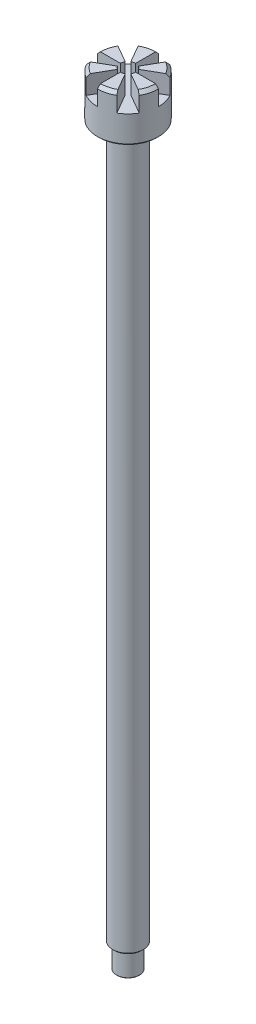
SolidWorks part; units mm, degrees
note: '?' marks a value the reader was unsure of.
ref_plane "Front Plane" through (0, 0, 0) normal (0, 0, 1) x (1, 0, 0)
ref_plane "Top Plane" through (0, 0, 0) normal (0, 1, 0) x (1, 0, 0)
ref_plane "Right Plane" through (0, 0, 0) normal (1, 0, 0) x (0, 0, -1)
sketch "Sketch1" plane through (0, 0, 0) normal (0, 0, 1) x (1, 0, 0)
  line L2 (0, 0) -> (0, 40)
  line L3 (0, 40) -> (20, 40)
  line L4 (20, 40) -> (20, 10)
  line L5 (20, 10) -> (10, 10)
  line L6 (10, 10) -> (10, 0)
  line L7 (10, 0) -> (0, 0)
  dimension "D1" = 10
  dimension "D2" = 10
  dimension "D4" = 40
  dimension "D6" = 20
revolve "Revolve1" add sketch "Sketch1" angle 360 about L2
ref_axis "Axis1" through (0, 40, 0) along (0, -1, 0)?
chamfer "Chamfer1" distance 2 angle 45 1 edges at (0, 40, -20)
sketch "Sketch2" plane through (0, 40, 0) normal (0, 1, 0) x (1, 0, 0)
  line L0 (0, 0) -> (0, 21.1426)
  line L1 (0, 21.1426) -> (12.2067, 21.1426)
  line L2 (12.2067, 21.1426) -> (0, 0)
  circle A0 centre (0, 0) radius 5
  circle M4 centre (0, 0) radius 18
  dimension "D2" = 10
  dimension "D1" = 30
extrude "Cut-Extrude1" cut sketch "Sketch2" against normal blind 12 contours A0 L2 L0 M4 | L2 L1 L0 M4
pattern_circular "CirPattern6" count 6 over 360 about axis through (0, 0, 0) along (0, 1, 0) of "Cut-Extrude1"
sketch "Sketch3" plane through (0, 40, 0) normal (0, 1, 0) x (1, 0, 0)
  circle A0 centre (0, 0) radius 5
  arc A1 (2.5, 4.3301) -> (0, 5) centre (0, 0) ccw construction
extrude "Cut-Extrude2" cut sketch "Sketch3" against normal up to surface (12 mm away)
chamfer "Chamfer2" distance 1 angle 45 2 edges at (0, 10, -20) (0, 10, -10)
sketch "Sketch4" plane through (0, 0, 0) normal (0, 0, 1) x (1, 0, 0)
  line L0 (0, 0) -> (0, -510)
  line L1 (0, -510) -> (10, -510)
  line L2 (10, -510) -> (10, 0)
  line L3 (10, 0) -> (0, 0)
  line L4 (10, 0) -> (10, 9) construction
  dimension "D1" = 510
revolve "Revolve2" add sketch "Sketch4" angle 360 about L0
sketch "Sketch5" plane through (0, -510, 0) normal (0, -1, 0) x (1, 0, 0)
  circle A0 centre (0, 0) radius 7.5
  dimension "D1" = 15
extrude "Cut-Extrude3" cut sketch "Sketch5" against normal blind 55 flip side to cut
chamfer "Chamfer3" distance 1 angle 45 1 edges at (10, -455, 0)
sketch "Sketch6" plane through (0, -510, 0) normal (0, -1, 0) x (1, 0, 0)
  circle A0 centre (0, 0) radius 30.6897
extrude "Cut-Extrude4" cut sketch "Sketch6" against normal blind 40
sketch "Sketch7" plane through (0, -470, 0) normal (0, -1, 0) x (1, 0, 0)
  circle A0 centre (0, 0) radius 6
  dimension "D1" = 12
extrude "Cut-Extrude5" cut sketch "Sketch7" against normal blind 25
sketch "Sketch8" plane through (0, -470, 0) normal (0, -1, 0) x (1, 0, 0)
  line L1 (0, 6.1743) -> (-1.45, 3.6628)
  line L2 (-1.45, 3.6628) -> (1.45, 3.6628)
  line L3 (1.45, 3.6628) -> (0, 6.1743)
  circle A0 centre (0, 4.5) radius 0.8372 construction
  dimension "D1" = 4.5
  dimension "D2" = 2.9
extrude "Cut-Extrude6" cut sketch "Sketch8" against normal up to surface (25 mm away) up to face at (6, -445, 0)
pattern_circular "CirPattern7" count 35 over 360 about axis through (0, 0, 0) along (0, 1, 0) of "Cut-Extrude6"
chamfer "Chamfer4" distance 0.3 angle 45 1 edges at (7.5, -470, 0)
